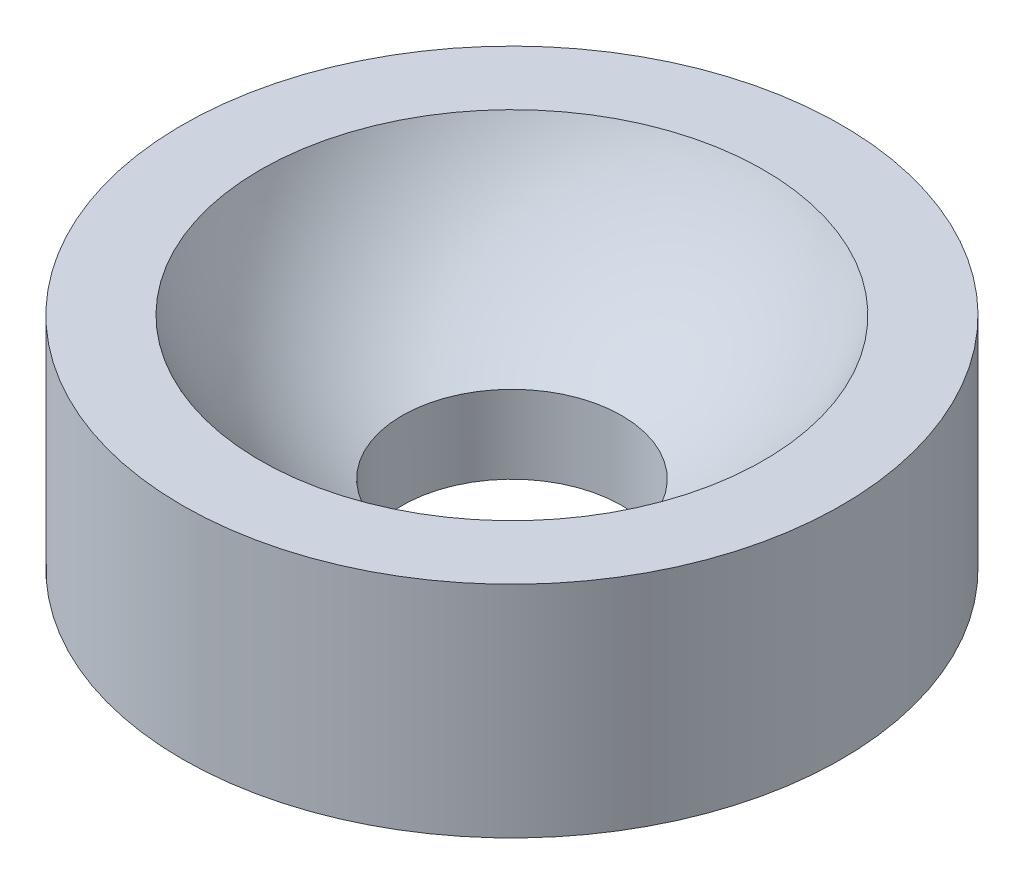
SolidWorks part; units mm, degrees
material "1023 Carbon Steel Sheet (SS)"
ref_plane "Front Plane" through (0, 0, 0) normal (0, 0, 1) x (1, 0, 0)
ref_plane "Top Plane" through (0, 0, 0) normal (0, 1, 0) x (1, 0, 0)
ref_plane "Right Plane" through (0, 0, 0) normal (1, 0, 0) x (0, 0, -1)
sketch "Sketch1" plane through (0, 0, 0) normal (0, 1, 0) x (1, 0, 0)
  circle A0 centre (0, 0) radius 6
  dimension "D1" = 12
extrude "Boss-Extrude1" add sketch "Sketch1" along normal blind 4
sketch "Sketch2" plane through (0, 0, 0) normal (0, 0, 1) x (1, 0, 0)
  line L0 (0, 1) -> (0, 11)
  arc A0 (0, 11) -> (0, 1) centre (0, 6) cw
  dimension "D1" = 10
  dimension "D2" = 1
revolve "Cut-Revolve1" cut sketch "Sketch2" angle 360 about L0
sketch "Sketch3" plane through (0, 0, 0) normal (0, -1, 0) x (1, 0, 0)
  circle A0 centre (0, 0) radius 2
  dimension "D1" = 4
extrude "Cut-Extrude1" cut sketch "Sketch3" against normal blind 4
